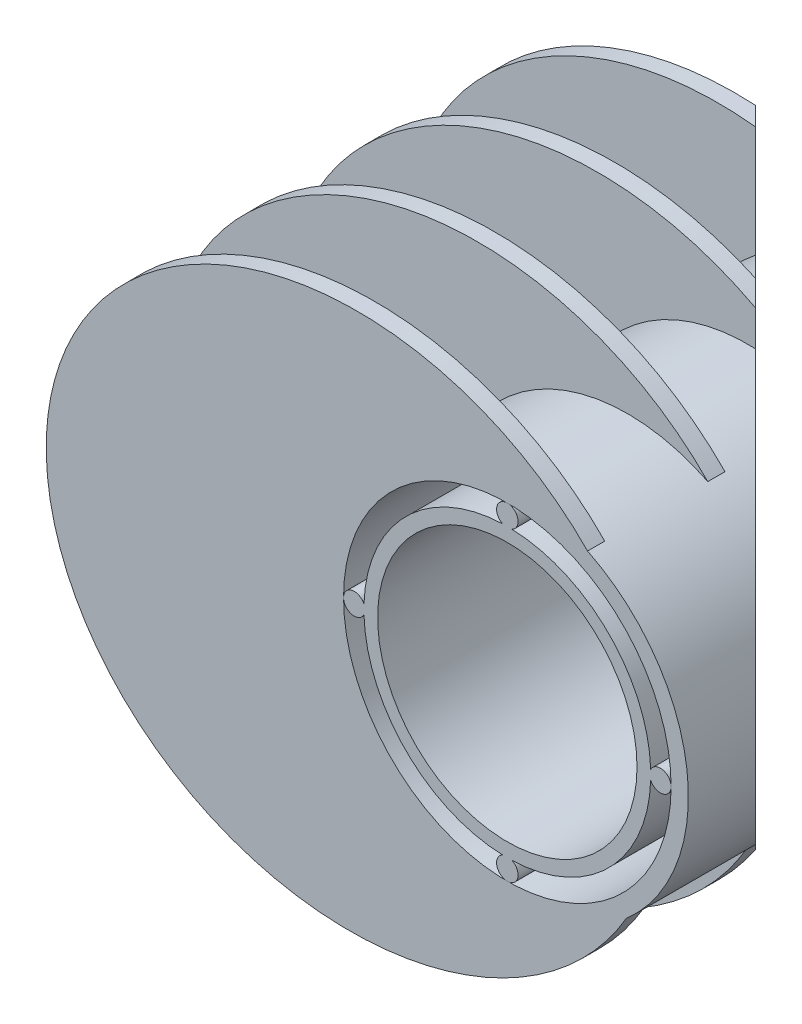
SolidWorks part; units mm, degrees
ref_plane "Front Plane" through (0, 0, 0) normal (0, 0, 1) x (1, 0, 0)
ref_plane "Top Plane" through (0, 0, 0) normal (0, 1, 0) x (1, 0, 0)
ref_plane "Right Plane" through (0, 0, 0) normal (1, 0, 0) x (0, 0, -1)
sketch "Sketch1" plane through (0, 0, 0) normal (0, 0, 1) x (1, 0, 0)
  circle A0 centre (0, 0) radius 21.08
  circle A1 centre (0, 0) radius 19.07
  dimension "D1" = 42.16
  dimension "D2" = 2.01
  dimension "D3" = 38.14
extrude "Boss-Extrude1" add sketch "Sketch1" against normal blind 50
sketch "Sketch2" plane through (0, 0, 0) normal (0, 1, 0) x (1, 0, 0)
  line L0 (-21.08, 50) -> (21.08, 7.84)
  line L1 (21.08, 0) -> (21.08, 50) construction
  line L2 (19.07, 50) -> (-19.07, 50) construction
  line L3 (21.08, 50) -> (-21.08, 50) construction
  line L4 (21.08, 7.84) -> (21.08, 50)
  line L5 (21.08, 50) -> (-21.08, 50)
  dimension "D1" = 45
sketch "Sketch3" plane through (0, 0, 0) normal (0, 0, 1) x (1, 0, 0)
  circle A0 centre (0, 0) radius 16.7
  circle A1 centre (0, 0) radius 15.1
  dimension "D1" = 33.4
  dimension "D2" = 1.6
extrude "Boss-Extrude2" add sketch "Sketch3" against normal blind 50 separate body
sketch "Sketch4" plane through (0, 0, 0) normal (0, 0, 1) x (1, 0, 0)
  circle A0 centre (0, -17.82) radius 1.25
  circle A6 centre (-17.82, 0) radius 1.25
  circle A7 centre (0, 17.82) radius 1.25
  circle A8 centre (17.82, 0) radius 1.25
  point P12 (0, 0)
  dimension "D1" = 4
  dimension "D4" = 2.5
  dimension "D5" = 17.82
extrude "Boss-Extrude3" add sketch "Sketch4" against normal blind 50
sketch "Sketch5" plane through (0, 0, 0) normal (0, 0, 1) x (1, 0, 0)
  circle A0 centre (0, 0) radius 21.08 construction
  arc A1 (9.3414, 18.8972) -> (13.8512, -15.8906) centre (0, 0) ccw
  ellipse E0 centre (-17.9146, -1.7871) end of major axis (17.82, 0) minor radius 31.4549 (9.3414, 18.8972) -> (13.8512, -15.8906) ccw
  point P1 (-32.1007, 1.363)
  point P7 (-32.1007, 25.6539)
  point P8 (-32.2194, 1.363)
  point P9 (17.82, 0)
  point P11 (-61.7285, -3.5943)
  point P12 (-53.6492, -3.5742)
extrude "Boss-Extrude4" add sketch "Sketch5" against normal blind 2
pattern_linear "LPattern2" count 4 spacing 14 along (0, 0, -1) of "Boss-Extrude4"
extrude "Cut-Extrude1" cut sketch "Sketch2" against normal mid plane 153
